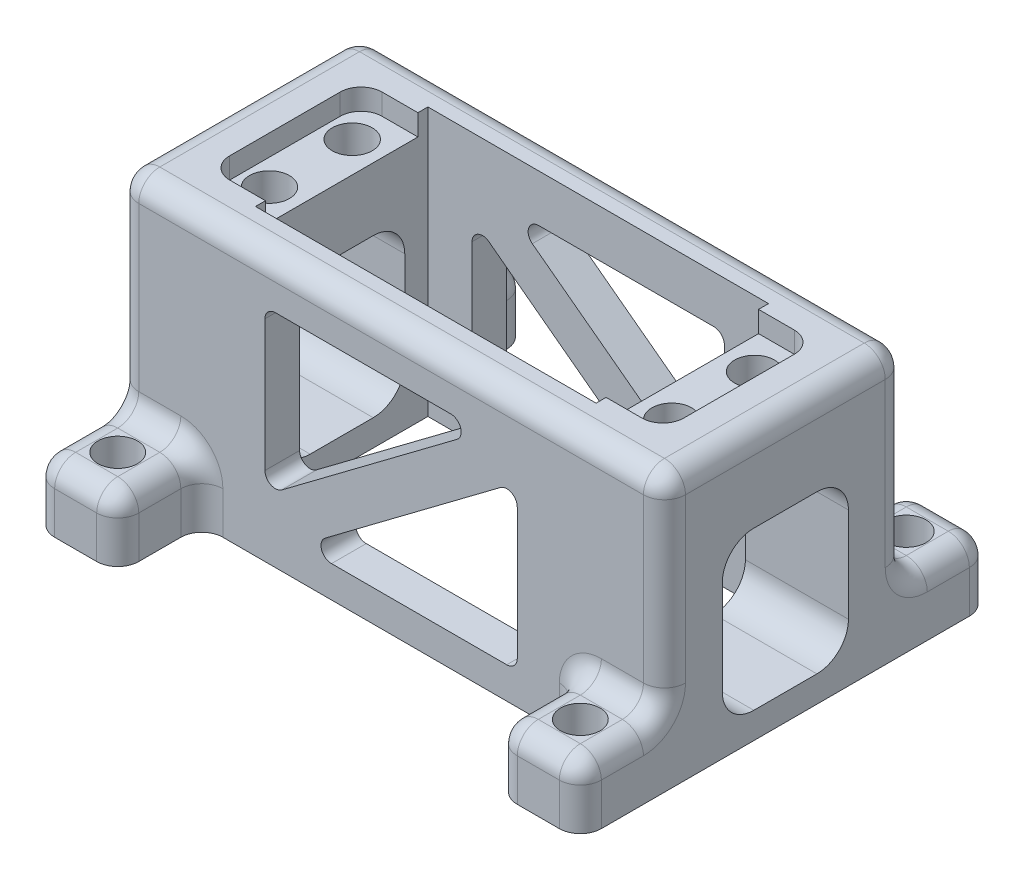
SolidWorks part; units mm, degrees
material "Olin QEA Filament - 40% infill "
ref_plane "Front Plane" through (0, 0, 0) normal (0, 0, 1) x (1, 0, 0)
ref_plane "Top Plane" through (0, 0, 0) normal (0, 1, 0) x (1, 0, 0)
ref_plane "Right Plane" through (0, 0, 0) normal (1, 0, 0) x (0, 0, -1)
sketch "Sketch1" plane through (0, 0, 0) normal (0, 1, 0) x (1, 0, 0)
  line L9 (-20.574, 10.414) -> (20.574, 10.414)
  line L10 (-20.574, 10.414) -> (-20.574, -10.414)
  line L11 (-20.574, -10.414) -> (20.574, -10.414)
  line L12 (20.574, 10.414) -> (20.574, -10.414)
  line L13 (-20.574, 10.414) -> (20.574, -10.414) construction
  line L14 (-20.574, -10.414) -> (20.574, 10.414) construction
  line L15 (-33.02, 14.605) -> (33.02, 14.605)
  line L16 (-33.02, 14.605) -> (-33.02, -14.605)
  line L17 (-33.02, -14.605) -> (33.02, -14.605)
  line L18 (33.02, 14.605) -> (33.02, -14.605)
  line L19 (-33.02, 14.605) -> (33.02, -14.605) construction
  line L20 (-33.02, -14.605) -> (33.02, 14.605) construction
  point P0 (0, 0)
  point P6 (0, 0)
  dimension "D1" = 41.148
  dimension "D2" = 20.828
  dimension "D3" = 66.04
  dimension "D4" = 29.21
extrude "Boss-Extrude1" add sketch "Sketch1" along normal blind 32.385
sketch "Sketch2" plane through (0, 32.385, 0) normal (0, 1, 0) x (1, 0, 0)
  line L0 (0, 14.605) -> (0, -14.605) construction
  line L1 (33.02, 14.605) -> (-33.02, 14.605) construction
  line L2 (-33.02, -14.605) -> (33.02, -14.605) construction
  line L3 (20.574, -10.414) -> (20.574, 10.414) construction
  line L4 (20.574, 9.2075) -> (24.892, 9.2075)
  line L5 (20.574, 9.2075) -> (20.574, -9.2075)
  line L6 (20.574, -9.2075) -> (24.892, -9.2075)
  line L7 (27.432, 6.6675) -> (27.432, -6.6675)
  line L8 (-20.574, -9.2075) -> (-24.892, -9.2075)
  line L9 (-27.432, 6.6675) -> (-27.432, -6.6675)
  line L10 (-20.574, 9.2075) -> (-24.892, 9.2075)
  line L11 (-20.574, 9.2075) -> (-20.574, -9.2075)
  arc A0 (24.892, -9.2075) -> (27.432, -6.6675) centre (24.892, -6.6675) ccw
  arc A1 (24.892, 9.2075) -> (27.432, 6.6675) centre (24.892, 6.6675) cw
  arc A2 (-24.892, -9.2075) -> (-27.432, -6.6675) centre (-24.892, -6.6675) cw
  arc A3 (-24.892, 9.2075) -> (-27.432, 6.6675) centre (-24.892, 6.6675) ccw
  point P12 (20.574, 0)
  point P13 (20.574, 0)
  point P18 (27.432, 9.2075)
  dimension "D3" = 2.54
  dimension "D1" = 18.415
  dimension "D2" = 6.858
extrude "Cut-Extrude1" cut sketch "Sketch2" against normal blind 2.54
sketch "Sketch3" plane through (0, 29.845, 0) normal (0, 1, 0) x (1, 0, 0)
  line L0 (24.3, 9.2075) -> (24.3, -9.2075) construction
  line L1 (24.892, 9.2075) -> (20.574, 9.2075) construction
  line L2 (20.574, -9.2075) -> (24.892, -9.2075) construction
  line L3 (0, 10.414) -> (0, -10.414) construction
  line L6 (24.3, 5) -> (24.3, -5)
  line L7 (20.574, 10.414) -> (-20.574, 10.414) construction
  line L8 (-20.574, -10.414) -> (20.574, -10.414) construction
  line L9 (-24.3, 9.2075) -> (-24.3, -9.2075) construction
  line L10 (-24.3, 5) -> (-24.3, -5)
  circle A0 centre (24.3, 5) radius 2.413
  circle A1 centre (24.3, -5) radius 2.413
  circle A2 centre (-24.3, -5) radius 2.413
  circle A3 centre (-24.3, 5) radius 2.413
  point P16 (24.3, 0)
  point P17 (24.3, 0)
  dimension "D2" = 4.826
  dimension "D3" = 4.826
  dimension "D1" = 10
  dimension "D4" = 48.6
extrude "Cut-Extrude2" cut sketch "Sketch3" against normal blind 10.16 contours A2 | A0 | A1 | A3 region at (25.958, 29.845, 3.342) region at (22.642, 29.845, -6.658) region at (-22.642, 29.845, 3.342)
sketch "Sketch4" plane through (0, 0, 0) normal (0, -1, 0) x (1, 0, 0)
  line L0 (0, 14.605) -> (0, -14.605) construction
  line L1 (-33.02, 14.605) -> (-22.86, 14.605)
  line L2 (-33.02, 14.605) -> (-33.02, 24.765)
  line L3 (-33.02, 24.765) -> (-22.86, 24.765)
  line L4 (-22.86, 14.605) -> (-22.86, 24.765)
  line L5 (-33.02, -14.605) -> (-22.86, -14.605)
  line L6 (-33.02, -14.605) -> (-33.02, -24.765)
  line L7 (-33.02, -24.765) -> (-22.86, -24.765)
  line L8 (-22.86, -14.605) -> (-22.86, -24.765)
  line L9 (-33.02, 14.605) -> (33.02, 14.605) construction
  line L10 (33.02, -14.605) -> (-33.02, -14.605) construction
  line L11 (33.02, -24.765) -> (22.86, -24.765)
  line L12 (22.86, -14.605) -> (22.86, -24.765)
  line L13 (33.02, -14.605) -> (22.86, -14.605)
  line L14 (33.02, -14.605) -> (33.02, -24.765)
  line L15 (33.02, 24.765) -> (22.86, 24.765)
  line L16 (22.86, 14.605) -> (22.86, 24.765)
  line L17 (33.02, 14.605) -> (22.86, 14.605)
  line L18 (33.02, 14.605) -> (33.02, 24.765)
  line M11 (33.02, 14.605) -> (-33.02, 14.605)
  dimension "D1" = 10.16
  dimension "D2" = 10.16
  dimension "D3" = 10.16
  dimension "D4" = 10.16
extrude "Boss-Extrude2" add sketch "Sketch4" against normal blind 7.62 contours L18 L15 L16 M11 | L2 L3 L4 L1 | L6 L7 L8 L5 | L12 L11 L14 L13 region at (27.94, 0, 19.685)
sketch "Sketch5" plane through (0, 0, 0) normal (0, -1, 0) x (1, 0, 0)
  line L0 (-33.02, 19.685) -> (33.02, 19.685) construction
  line L1 (-33.02, -24.765) -> (-33.02, 24.765) construction
  line L2 (33.02, 24.765) -> (33.02, -24.765) construction
  line L3 (-33.02, -19.685) -> (33.02, -19.685) construction
  line L4 (27.94, 24.765) -> (27.94, -24.765) construction
  line L5 (33.02, 24.765) -> (22.86, 24.765) construction
  line L6 (33.02, -24.765) -> (22.86, -24.765) construction
  line L7 (-27.94, -24.765) -> (-27.94, 24.765) construction
  line L8 (-33.02, -24.765) -> (-22.86, -24.765) construction
  line L9 (-33.02, 24.765) -> (-22.86, 24.765) construction
  line L10 (-22.86, -14.605) -> (-22.86, -24.765) construction
  line L11 (-22.86, 14.605) -> (-22.86, 24.765) construction
  circle A0 centre (27.94, 19.685) radius 2.3876
  circle A1 centre (27.94, -19.685) radius 2.3876
  circle A2 centre (-27.94, -19.685) radius 2.3876
  circle A3 centre (-27.94, 19.685) radius 2.3876
  point P30 (-22.86, -19.685)
  point P33 (-22.86, 19.685)
  dimension "D3" = 4.7752
  dimension "D4" = 4.7752
  dimension "D5" = 4.7752
  dimension "D6" = 4.7752
extrude "Cut-Extrude3" cut sketch "Sketch5" against normal through all contours A3 | A0 | A2 | A1
fillet "Fillet1" radius 2.54 36 edges at (22.86, 3.81, -14.605) (33.02, 7.62, -19.685) (-22.86, 3.81, -14.605) (-33.02, 7.62, 19.685) (33.02, 7.62, 19.685) (-33.02, 32.385, 0) (33.02, 32.385, 0) (33.02, 3.81, -24.765) (22.86, 3.81, -24.765) (22.86, 7.62, -19.685) (27.94, 7.62, -24.765) (27.94, 7.62, -14.605) (0, 32.385, -14.605) (33.02, 20.0025, -14.605) (-22.86, 3.81, -24.765) (-33.02, 3.81, -24.765) (-27.94, 7.62, -24.765) (-22.86, 7.62, -19.685) (-27.94, 7.62, -14.605) (-33.02, 7.62, -19.685) (-33.02, 20.0025, -14.605) (-22.86, 3.81, 24.765) (-33.02, 3.81, 24.765) (22.86, 3.81, 24.765) (33.02, 3.81, 24.765) (-27.94, 7.62, 24.765) (27.94, 7.62, 24.765) (22.86, 7.62, 19.685) (-22.86, 7.62, 19.685) (22.86, 3.81, 14.605) (-22.86, 3.81, 14.605) (-27.94, 7.62, 14.605) (27.94, 7.62, 14.605) (0, 32.385, 14.605) (33.02, 20.0025, 14.605) (-33.02, 20.0025, 14.605)
sketch "Sketch6" plane through (33.02, 0, 0) normal (1, 0, 0) x (0, 0, -1)
  line L1 (-3.81, 22.225) -> (3.81, 22.225)
  line L2 (-7.62, 18.415) -> (-7.62, 6.985)
  line L3 (-3.81, 3.175) -> (3.81, 3.175)
  line L4 (7.62, 18.415) -> (7.62, 6.985)
  line L5 (-7.62, 22.225) -> (7.62, 3.175) construction
  line L6 (-7.62, 3.175) -> (7.62, 22.225) construction
  line L7 (0, 0) -> (0, 29.845) construction
  line L8 (12.065, 29.845) -> (-12.065, 29.845) construction
  arc A0 (3.81, 3.175) -> (7.62, 6.985) centre (3.81, 6.985) ccw
  arc A1 (-7.62, 6.985) -> (-3.81, 3.175) centre (-3.81, 6.985) ccw
  arc A2 (3.81, 22.225) -> (7.62, 18.415) centre (3.81, 18.415) cw
  arc A3 (-3.81, 22.225) -> (-7.62, 18.415) centre (-3.81, 18.415) ccw
  point P0 (0, 12.7)
  dimension "D4" = 3.81
  dimension "D2" = 19.05
  dimension "D3" = 15.24
  dimension "D5" = 3.175
extrude "Cut-Extrude4" cut sketch "Sketch6" against normal through all contours A3 L2 A1 L3 A0 L4 A2 L1
sketch "Sketch9" plane through (0, 0, -14.605) normal (0, 0, -1) x (-1, 0, 0)
  line L0 (-20.32, 0) -> (20.32, 0) construction
  line L1 (-13.97, 26.67) -> (7.1967, 26.67)
  line L2 (-15.24, 25.4) -> (-15.24, 9.525)
  line L3 (-7.1967, 3.81) -> (13.97, 3.81)
  line L4 (15.24, 20.955) -> (15.24, 5.08)
  line L5 (-15.24, 26.67) -> (15.24, 3.81) construction
  line L6 (-15.24, 3.81) -> (15.24, 26.67) construction
  line L7 (0, 0) -> (0, 32.385) construction
  line L8 (-30.48, 32.385) -> (30.48, 32.385) construction
  line L9 (-7.9587, 6.096) -> (13.208, 21.971)
  line L10 (7.9587, 24.384) -> (-13.208, 8.509)
  line L11 (-4.919, 14.7258) -> (-1.871, 10.6618) construction
  arc A0 (13.208, 21.971) -> (15.24, 20.955) centre (13.97, 20.955) cw
  arc A1 (13.97, 3.81) -> (15.24, 5.08) centre (13.97, 5.08) ccw
  arc A2 (-7.9587, 6.096) -> (-7.1967, 3.81) centre (-7.1967, 5.08) ccw
  arc A3 (-13.208, 8.509) -> (-15.24, 9.525) centre (-13.97, 9.525) cw
  arc A4 (7.9587, 24.384) -> (7.1967, 26.67) centre (7.1967, 25.4) ccw
  arc A5 (-13.97, 26.67) -> (-15.24, 25.4) centre (-13.97, 25.4) ccw
  point P0 (0, 15.24)
  point P18 (-3.395, 12.6938)
  dimension "D5" = 1.27
  dimension "D1" = 3.81
  dimension "D2" = 30.48
  dimension "D3" = 22.86
  dimension "D4" = 5.08
extrude "Cut-Extrude5" cut sketch "Sketch9" against normal up to next contours L1 A4 L10 A3 L2 A5 | L9 A0 L4 A1 L3 A2
sketch "Sketch10" plane through (0, 0, 14.605) normal (0, 0, 1) x (1, 0, 0)
  line L0 (0, 0) -> (0, 29.845) construction
  line L1 (30.48, 29.845) -> (-30.48, 29.845) construction
  line L2 (-20.32, 0) -> (20.32, 0) construction
  line L3 (-13.97, 26.67) -> (7.1967, 26.67)
  line L4 (-15.24, 25.4) -> (-15.24, 9.525)
  line L5 (-7.1967, 3.81) -> (13.97, 3.81)
  line L6 (15.24, 20.955) -> (15.24, 5.08)
  line L7 (-15.24, 26.67) -> (15.24, 3.81) construction
  line L8 (-15.24, 3.81) -> (15.24, 26.67) construction
  line L9 (-7.9587, 6.096) -> (13.208, 21.971)
  line L10 (-13.208, 8.509) -> (7.9587, 24.384)
  line L11 (-3.3383, 9.5613) -> (-6.3863, 13.6253) construction
  arc A0 (-7.9587, 6.096) -> (-7.1967, 3.81) centre (-7.1967, 5.08) ccw
  arc A1 (13.97, 3.81) -> (15.24, 5.08) centre (13.97, 5.08) ccw
  arc A2 (13.208, 21.971) -> (15.24, 20.955) centre (13.97, 20.955) cw
  arc A3 (7.9587, 24.384) -> (7.1967, 26.67) centre (7.1967, 25.4) ccw
  arc A4 (-13.208, 8.509) -> (-15.24, 9.525) centre (-13.97, 9.525) cw
  arc A5 (-13.97, 26.67) -> (-15.24, 25.4) centre (-13.97, 25.4) ccw
  point P5 (0, 15.24)
  point P18 (-4.8623, 11.5933)
  dimension "D5" = 1.27
  dimension "D1" = 30.48
  dimension "D2" = 22.86
  dimension "D3" = 3.81
  dimension "D4" = 5.08
extrude "Cut-Extrude6" cut sketch "Sketch10" against normal up to next contours A2 L9 A0 L5 A1 L6 | L3 A3 L10 A4 L4 A5 region at (6.607, 10.3777, 14.605)
